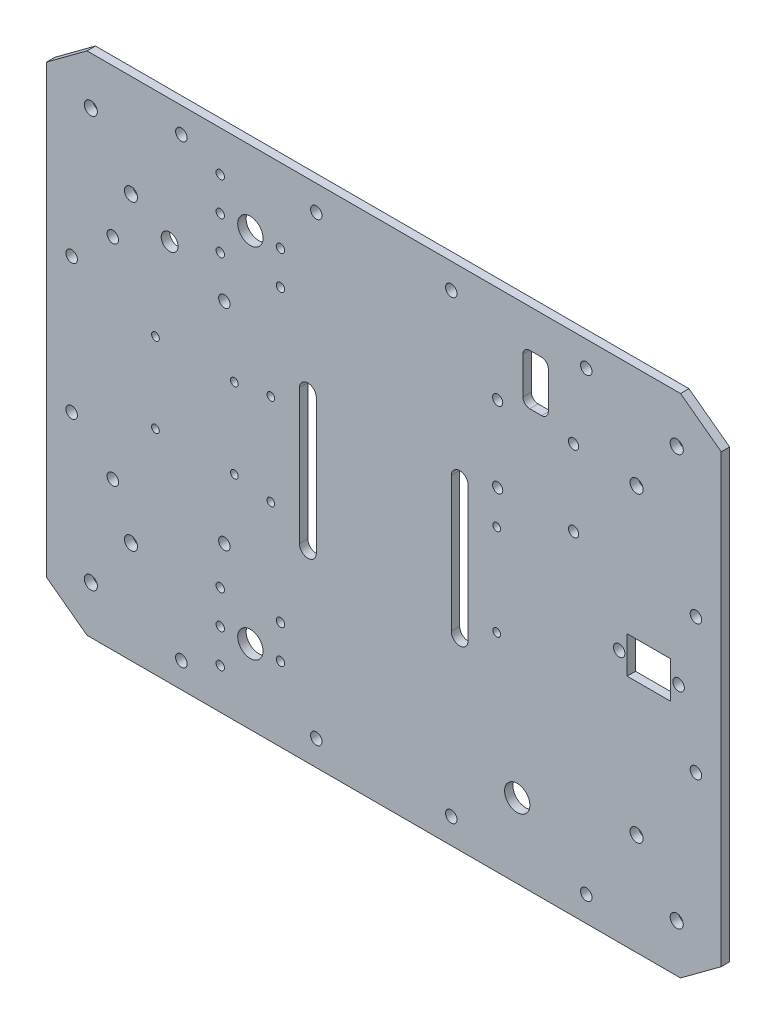
SolidWorks part; units mm, degrees
material "Thornel Mat VMA"
ref_plane "Front Plane" through (0, 0, 0) normal (0, 0, 1) x (1, 0, 0)
ref_plane "Top Plane" through (0, 0, 0) normal (0, 1, 0) x (1, 0, 0)
ref_plane "Right Plane" through (0, 0, 0) normal (1, 0, 0) x (0, 0, -1)
sketch "Sketch1" plane through (0, 0, 0) normal (0, 0, 1) x (1, 0, 0)
  line L0 (-127, 0) -> (127, 0) construction
  line L1 (0, -95.25) -> (0, 95.25) construction
  line L2 (-107.95, 0) -> (-107.95, 41.011) construction
  line L3 (-107.95, 41.011) -> (-95.25, 41.011) construction
  line L4 (-95.25, 41.011) -> (-79.9365, 52.3423) construction
  line L5 (-79.9365, 52.3423) -> (-79.9365, 76.2) construction
  line L6 (-79.9365, 76.2) -> (0, 76.2) construction
  line L7 (-95.25, 41.011) -> (-127, 83.9186) construction
  line L8 (-79.9365, 52.3423) -> (-111.6865, 95.25) construction
  line L9 (-111.6865, -95.25) -> (-127, -83.9186)
  line L10 (111.6865, -95.25) -> (127, -83.9186)
  line L11 (111.6865, 95.25) -> (127, 83.9186)
  line L12 (-87.5933, 46.6767) -> (-95.1475, 56.8856) construction
  line L13 (-95.1475, 56.8856) -> (-110.256, 77.3036) construction
  line L24 (127, -83.9186) -> (127, 83.9186)
  line L26 (111.6865, 95.25) -> (-111.6865, 95.25)
  line L27 (-111.6865, 95.25) -> (-127, 83.9186)
  line L28 (-127, 83.9186) -> (-127, -83.9186)
  line L30 (-111.6865, -95.25) -> (111.6865, -95.25)
  circle A0 centre (-95.1475, 56.8856) radius 2.4638
  circle A1 centre (-110.256, 77.3036) radius 2.4638
  circle A2 centre (110.256, 77.3036) radius 2.4638
  circle A3 centre (95.1475, 56.8856) radius 2.4638
  circle A4 centre (-110.256, -77.3036) radius 2.4638
  circle A5 centre (-95.1475, -56.8856) radius 2.4638
  circle A6 centre (110.256, -77.3036) radius 2.4638
  circle A7 centre (95.1475, -56.8856) radius 2.4638
  point P12 (0, 0)
  dimension "D1" = 190.5
  dimension "D2" = 254
  dimension "D3" = 19.05
  dimension "D4" = 19.05
  dimension "D5" = 12.7
  dimension "D6" = 19.05
  dimension "D7" = 143.5
  dimension "D8" = 12.7
  dimension "D9" = 25.4
extrude "Boss-Extrude1" add sketch "Sketch1" along normal blind 3.175
sketch "Sketch2" plane through (0, 0, 3.175) normal (0, 0, 1) x (1, 0, 0)
  line L0 (-127, 0) -> (127, 0) construction
  line L1 (-127, 83.9186) -> (-127, -83.9186) construction
  line L2 (127, -83.9186) -> (127, 83.9186) construction
  line L3 (57.15, 65.0875) -> (57.15, -65.0875) construction
  line L4 (38.1, 65.0875) -> (76.2, 65.0875)
  line L5 (38.1, 65.0875) -> (38.1, -65.0875)
  line L6 (38.1, -65.0875) -> (76.2, -65.0875)
  line L7 (76.2, 65.0875) -> (76.2, -65.0875)
  line L8 (38.1, 65.0875) -> (76.2, -65.0875) construction
  line L9 (38.1, -65.0875) -> (76.2, 65.0875) construction
  line L10 (57.15, 58.7375) -> (47.625, 58.7375) construction
  line L11 (47.625, 58.7375) -> (38.1, 58.7375) construction
  line L12 (99.7726, 0) -> (99.7726, 35.1373) construction
  line L13 (91.5811, -6.9215) -> (107.9641, -6.9215)
  line L14 (91.5811, -6.9215) -> (91.5811, 6.9215)
  line L15 (91.5811, 6.9215) -> (107.9641, 6.9215)
  line L16 (107.9641, -6.9215) -> (107.9641, 6.9215)
  line L17 (91.5811, -6.9215) -> (107.9641, 6.9215) construction
  line L18 (91.5811, 6.9215) -> (107.9641, -6.9215) construction
  circle A0 centre (42.8625, 58.7375) radius 2.159
  circle A1 centre (42.8625, -58.7375) radius 2.159
  circle A2 centre (71.4375, -58.7375) radius 2.159
  circle A3 centre (71.4375, 58.7375) radius 2.159
  circle A4 centre (110.9486, 0) radius 2.159
  circle A5 centre (88.5966, 0) radius 2.159
  point P6 (57.15, 0)
  point P17 (42.8625, 58.7375)
  point P25 (99.7726, 0)
  dimension "D6" = 13.843
  dimension "D8" = 11.176
  dimension "D1" = 38.1
  dimension "D2" = 130.175
  dimension "D3" = 6.35
  dimension "D4" = 9.525
  dimension "D5" = 69.85
  dimension "D7" = 16.383
extrude "Cut-Extrude1" cut sketch "Sketch2" against normal through all contours L13 L16 L15 L14 | A5 | A4 region at (99.7726, 0, 3.175) region at (110.9486, 0, 3.175) region at (88.5966, 0, 3.175)
sketch "Sketch3" plane through (0, 0, 3.175) normal (0, 0, 1) x (1, 0, 0)
  line L0 (0, 95.25) -> (0, -95.25) construction
  line L1 (111.6865, 95.25) -> (-111.6865, 95.25) construction
  line L2 (-111.6865, -95.25) -> (111.6865, -95.25) construction
  line L3 (127, 0) -> (-127, 0) construction
  line L4 (127, -83.9186) -> (127, 83.9186) construction
  line L5 (-127, 83.9186) -> (-127, -83.9186) construction
  line L8 (119.3433, -89.5843) -> (111.789, -79.3753) construction
  line L10 (111.6865, -95.25) -> (127, -83.9186) construction
  line L11 (111.6865, -95.25) -> (127, -83.9186)
  circle A0 centre (111.789, -79.3753) radius 1.9844
  circle A1 centre (96.6805, -58.9574) radius 1.9844
  dimension "D2" = 3.9688
  dimension "D3" = 3.9688
  dimension "D1" = 12.7
  dimension "D4" = 25.4
sketch "Sketch5" plane through (0, 0, 0) normal (0, 0, -1) x (-1, 0, 0)
  line L0 (-127, 0) -> (127, 0) construction
  line L1 (105.9946, 43.5) -> (55.9947, 43.5) construction
  line L2 (105.9946, 43.5) -> (105.9946, -43.5) construction
  line L3 (105.9946, -43.5) -> (55.9947, -43.5) construction
  line L4 (55.9947, 43.5) -> (55.9947, -43.5) construction
  line L5 (89.2369, 18.0341) -> (89.2369, -18.0339)
  line L6 (67.8946, 95.25) -> (67.8946, -95.25) construction
  line L7 (-71.4375, 58.7375) -> (-42.8625, 58.7375) construction
  line L8 (0, 64.0679) -> (0, -49.8393) construction
  line L9 (-42.5, 17.2) -> (42.5, 17.2) construction
  line L10 (-42.5, 17.2) -> (-42.5, -17.2) construction
  line L11 (-42.5, -17.2) -> (42.5, -17.2) construction
  line L12 (42.5, 17.2) -> (42.5, -17.2) construction
  line L13 (-42.5, 17.2) -> (42.5, -17.2) construction
  line L14 (-42.5, -17.2) -> (42.5, 17.2) construction
  line L15 (80.5946, 60.96) -> (31.75, 60.96) construction
  line L16 (61.5446, -67.31) -> (-87.4336, -67.31) construction
  line L17 (50.2154, -67.31) -> (50.2154, 67.31) construction
  line L18 (50.2154, 67.31) -> (38.8861, 67.31) construction
  line L19 (-28.575, 25.4) -> (-28.575, -25.4) construction
  line L21 (-127, -83.9186) -> (-127, 83.9186) construction
  line L22 (-57.15, 71.4375) -> (80.5946, 71.4375) construction
  line L23 (80.5946, 71.4375) -> (80.5946, 48.58) construction
  line L24 (-71.4375, 58.7375) -> (-71.4375, 30.1625) construction
  line L25 (80.5946, -77.0458) -> (80.5946, 48.58) construction
  line L26 (127, 0) -> (-127, 0) construction
  line L27 (80.9947, 0) -> (80.9947, -8419.0368) construction
  line L28 (-25.4, 25.4) -> (-25.4, -25.4)
  line L29 (-31.75, 25.4) -> (-31.75, -25.4)
  line L30 (28.575, 25.4) -> (28.575, -25.4) construction
  line L31 (25.4, 25.4) -> (25.4, -25.4)
  line L32 (31.75, 25.4) -> (31.75, -25.4)
  line L33 (71.0787, 0) -> (71.0787, 12.3782) construction
  line L34 (53.2197, 18.0341) -> (89.2369, 18.0341)
  line L35 (53.2197, 18.0341) -> (53.2197, -18.0339)
  line L36 (53.2197, -18.0339) -> (89.2369, -18.0339)
  line L37 (-52.3875, 61.9125) -> (-61.9125, 61.9125)
  line L38 (-52.3875, 61.9125) -> (-52.3875, 80.9625)
  line L39 (-52.3875, 80.9625) -> (-61.9125, 80.9625)
  line L40 (-57.15, 58.7375) -> (-57.15, 95.25) construction
  line L41 (-61.9125, 61.9125) -> (-61.9125, 80.9625)
  line L42 (-52.3875, 61.9125) -> (-61.9125, 80.9625) construction
  line L43 (-52.3875, 80.9625) -> (-61.9125, 61.9125) construction
  line L44 (-42.8625, 58.7375) -> (-71.4375, 30.1625) construction
  line L45 (-42.8625, 30.1625) -> (-71.4375, 30.1625) construction
  line L46 (-42.8625, 30.1625) -> (-42.8625, 58.7375) construction
  circle A0 centre (61.5446, -54.61) radius 1.5875
  circle A1 centre (61.5446, -67.31) radius 1.5875
  circle A2 centre (80.5946, 48.58) radius 3.175
  circle A3 centre (-71.4375, 58.7375) radius 1.9177
  circle A4 centre (61.5446, 54.61) radius 1.5875
  circle A5 centre (61.5446, -80.01) radius 1.5875
  circle A6 centre (-50.2154, -67.31) radius 4.7625
  circle A7 centre (50.2154, -67.31) radius 4.7625
  circle A8 centre (61.5446, 67.31) radius 1.5875
  circle A9 centre (61.5446, 80.01) radius 1.5875
  circle A10 centre (50.2154, 67.31) radius 4.7625
  circle A11 centre (-71.4375, 30.1625) radius 1.9177
  circle A12 centre (59.9952, 39.4995) radius 2.159
  circle A13 centre (101.9941, 39.4995) radius 2.159
  circle A14 centre (59.9952, -39.4995) radius 2.159
  circle A15 centre (101.9941, -39.4995) radius 2.159
  circle A16 centre (38.8861, 67.31) radius 1.5875
  circle A17 centre (38.8861, 54.61) radius 1.5875
  circle A18 centre (38.8861, -67.31) radius 1.5875
  circle A19 centre (38.8861, -54.61) radius 1.5875
  arc A20 (-25.4, 25.4) -> (-31.75, 25.4) centre (-28.575, 25.4) ccw
  arc A21 (-31.75, -25.4) -> (-25.4, -25.4) centre (-28.575, -25.4) ccw
  arc A22 (25.4, 25.4) -> (31.75, 25.4) centre (28.575, 25.4) cw
  arc A23 (31.75, -25.4) -> (25.4, -25.4) centre (28.575, -25.4) cw
  circle A24 centre (56.2197, 15.0341) radius 1.4478
  circle A25 centre (56.2197, -15.0341) radius 1.4478
  circle A26 centre (85.9377, -15.0341) radius 1.4478
  circle A27 centre (85.9377, 15.0341) radius 1.4478
  circle A28 centre (-42.5, 17.2) radius 1.4542
  circle A29 centre (-42.5, -17.2) radius 1.4541
  circle A30 centre (42.5, -17.2) radius 1.4541
  circle A31 centre (42.5, 17.2) radius 1.4542
  circle A32 centre (-42.8625, 58.7375) radius 1.9177
  circle A33 centre (-42.8625, 30.1625) radius 1.9177
  point P0 (80.9947, 0)
  point P9 (0, 0)
  point P77 (-28.575, 0)
  point P84 (28.575, 0)
  point P89 (71.0787, 0)
  dimension "D10" = 6.35
  dimension "D15" = 2.9997
  dimension "D17" = 3.8354
  dimension "D18" = 3.8354
  dimension "D25" = 4.0005
  dimension "D45" = 2.8956
  dimension "D9" = 3.8354
  dimension "D13" = 14.859
  dimension "D14" = 3
  dimension "D20" = 9.525
  dimension "D8" = 111.76
  dimension "D19" = 19.05
  dimension "D16" = 3.8354
  dimension "D1" = 87.0001
  dimension "D2" = 49.9999
  dimension "D4" = 34.4
  dimension "D5" = 85
  dimension "D6" = 6.35
  dimension "D7" = 12.7
  dimension "D11" = 5.08
  dimension "D12" = 25.4
  dimension "D26" = 4.0005
  dimension "D38" = 50.8
  dimension "D39" = 6.35
  dimension "D40" = 28.575
  dimension "D41" = 36.0172
  dimension "D42" = 36.068
  dimension "D44" = 3
extrude "Cut-Extrude2" cut sketch "Sketch5" against normal through all contours A2 | A14 | A15 | A13 | A12 | L29 A21 L28 A20 | A23 L4 A22 L31 | A23 L32 A22 L4 | A27 | A24 | A25 | A26
sketch "Sketch6" plane through (0, 0, 0) normal (0, 0, -1) x (-1, 0, 0)
  line L0 (0, 0) -> (-135.1326, 0) construction
  line L1 (0, 0) -> (0, -95.25) construction
  line L2 (111.6865, -95.25) -> (-111.6865, -95.25) construction
  line L3 (-76.2, -95.25) -> (-76.2, -85.725) construction
  line L4 (117.475, 0) -> (117.475, -25.4) construction
  line L5 (127, 0) -> (-127, 0) construction
  line L6 (127, 83.9186) -> (127, -83.9186) construction
  circle A0 centre (-76.2, -85.725) radius 2.159
  circle A1 centre (-25.4, -85.725) radius 2.159
  circle A2 centre (25.4, -85.725) radius 2.159
  circle A3 centre (76.2, -85.725) radius 2.159
  circle A4 centre (76.2, 85.725) radius 2.159
  circle A5 centre (25.4, 85.725) radius 2.159
  circle A6 centre (-25.4, 85.725) radius 2.159
  circle A7 centre (-76.2, 85.725) radius 2.159
  circle A8 centre (117.475, -25.4) radius 2.159
  circle A9 centre (117.475, 25.4) radius 2.159
  circle A10 centre (-117.475, 25.4) radius 2.159
  circle A11 centre (-117.475, -25.4) radius 2.159
  dimension "D2" = 9.525
  dimension "D3" = 76.2
  dimension "D5" = 9.525
  dimension "D6" = 25.4
  dimension "D4" = 4
extrude "Cut-Extrude3" cut sketch "Sketch6" against normal through all
extrude "Cut-Extrude4" cut sketch "Sketch5<3>" against normal through all contours A28 | A29 | A31 | A30
sketch "Sketch5<3>" plane through (0, 0, 0) normal (0, 0, -1) x (-1, 0, 0) same geometry as "Sketch5"
extrude "Cut-Extrude5" cut sketch "Sketch5<4>" against normal through all contours A10 | A9 | A8 | A4 | A0 | A1 | A5 | A7 | A6
sketch "Sketch5<4>" plane through (0, 0, 0) normal (0, 0, -1) x (-1, 0, 0) same geometry as "Sketch5"
extrude "Cut-Extrude6" cut sketch "Sketch5<5>" against normal blind 2.54 contours A18 | A17 | A16
sketch "Sketch5<5>" plane through (0, 0, 0) normal (0, 0, -1) x (-1, 0, 0) same geometry as "Sketch5"
extrude "Cut-Extrude7" cut sketch "Sketch5<6>" against normal through all contours A17 | A18 | A16
sketch "Sketch5<6>" plane through (0, 0, 0) normal (0, 0, -1) x (-1, 0, 0) same geometry as "Sketch5"
sketch "Sketch8" plane through (0, 0, 3.175) normal (0, 0, 1) x (1, 0, 0)
extrude "Cut-Extrude8" cut sketch "Sketch5<7>" against normal blind 2.54 and the other way blind 7.62 contours L41 L37 L38 L39 | A3 | A11 | A19 | A32 | A33 region at (57.15, 71.4375, 0) region at (71.4375, 58.7375, 0) region at (71.4375, 30.1625, 0) region at (-38.8861, -54.61, 0)
sketch "Sketch5<7>" plane through (0, 0, 0) normal (0, 0, -1) x (-1, 0, 0) same geometry as "Sketch5"
extrude "Cut-Extrude9" cut sketch "Sketch5<9>" against normal through all contours A11 | A33 | A32 | A3
sketch "Sketch5<9>" plane through (0, 0, 0) normal (0, 0, -1) x (-1, 0, 0) same geometry as "Sketch5"
extrude "Cut-Extrude13" cut sketch "Sketch5<12>" against normal through all both and the other way through all contours A11 rebuild error yes
sketch "Sketch5<12>" plane through (0, 0, 0) normal (0, 0, -1) x (-1, 0, 0) same geometry as "Sketch5"
extrude "Cut-Extrude14" cut sketch "Sketch5<13>" against normal through all contours A19
sketch "Sketch5<13>" plane through (0, 0, 0) normal (0, 0, -1) x (-1, 0, 0) same geometry as "Sketch5"
extrude "Cut-Extrude17" cut sketch "Sketch5<15>" against normal through all both and the other way through all contours L39 L41 L37 L38
sketch "Sketch5<15>" plane through (0, 0, 0) normal (0, 0, -1) x (-1, 0, 0) same geometry as "Sketch5"
fillet "Fillet1" radius 2.54 1 edges at (61.9125, 80.9625, 1.5875) type face fillet first side face at (61.9125, 71.4375, 1.5875) second side face at (57.15, 80.9625, 1.5875)
fillet "Fillet2" radius 2.54 1 edges at (52.3875, 80.9625, 1.5875) type face fillet first side face at (55.88, 80.9625, 1.5875) second side face at (52.3875, 71.4375, 1.5875)
fillet "Fillet3" radius 2.54 1 edges at (52.3875, 61.9125, 1.5875) type face fillet first side face at (57.15, 61.9125, 1.5875) second side face at (52.3875, 70.1675, 1.5875)
fillet "Fillet4" radius 2.54 1 edges at (61.9125, 61.9125, 1.5875) type face fillet first side face at (58.42, 61.9125, 1.5875) second side face at (61.9125, 70.1675, 1.5875)
